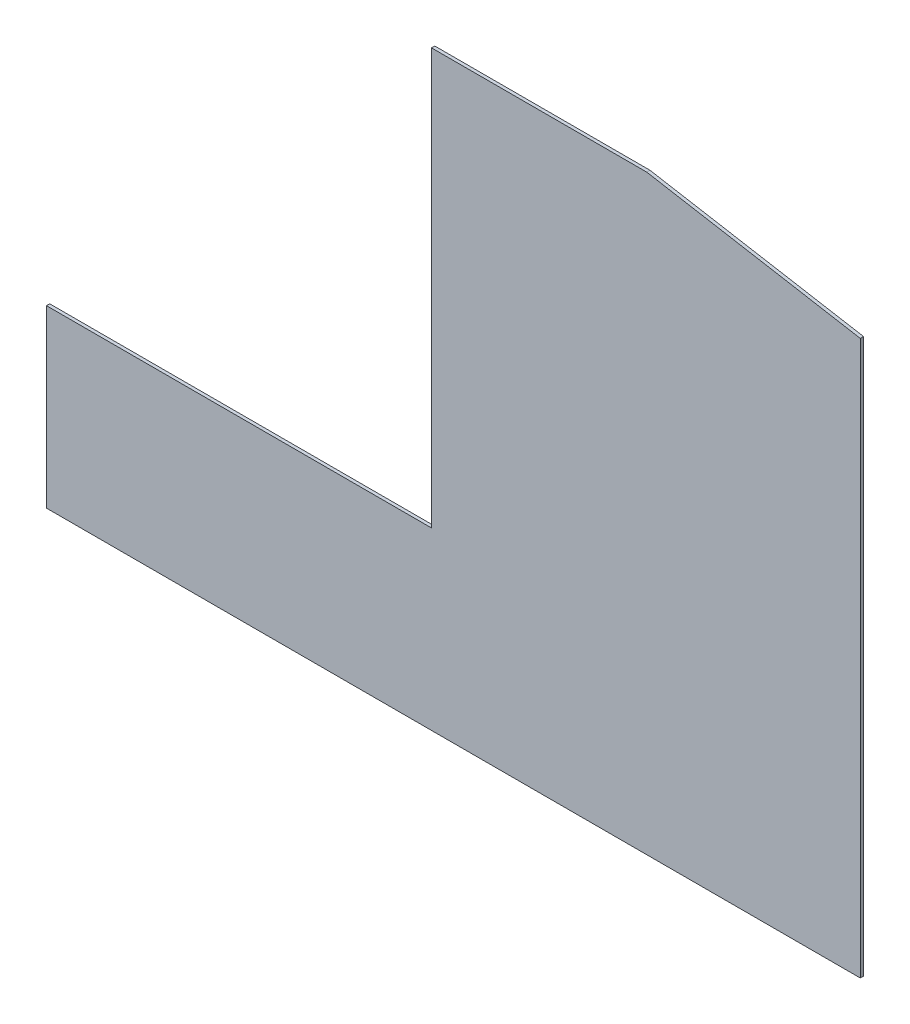
SolidWorks part; units mm, degrees
material "Hardox"
ref_plane "Ön Düzlem" through (0, 0, 0) normal (0, 0, 1) x (1, 0, 0)
ref_plane "Üst Düzlem" through (0, 0, 0) normal (0, 1, 0) x (1, 0, 0)
ref_plane "Sağ Düzlem" through (0, 0, 0) normal (1, 0, 0) x (0, 0, -1)
sketch "Çizim1" plane through (0, 0, 0) normal (0, 0, 1) x (1, 0, 0)
  line L0 (0, 0) -> (0, 1720)
  line L1 (0, 1720) -> (660, 1835)
  line L2 (660, 1835) -> (1855, 1835)
  line L3 (1855, 1835) -> (2515, 1720)
  line L4 (2515, 1720) -> (2515, 0)
  line L5 (2515, 0) -> (0, 0)
  dimension "D1" = 660
  dimension "D2" = 2515
  dimension "D3" = 660
  dimension "D4" = 1720
  dimension "D5" = 115
base flange "Taban-Flanş1" sketch "Çizim1" thickness 10 reverse thickness direction no parameters "D1"=6
sketch "Çizim6" plane through (0, 0, 0) normal (0, 0, 1) x (1, 0, 0)
  line L0 (1855, 1835) -> (660, 1835) construction
  line L1 (1190, 1835) -> (0, 1835)
  line L2 (1190, 1835) -> (1190, 550)
  line L3 (1190, 550) -> (0, 550)
  line L4 (0, 1835) -> (0, 550)
  line L5 (0, 1720) -> (0, 0) construction
  line L6 (0, 0) -> (2515, 0) construction
  line L7 (2515, 0) -> (2515, 1720) construction
  line L8 (0, 0) -> (2515, 0)
  line L9 (0, 0) -> (0, 8)
  line L10 (0, 8) -> (2515, 8)
  line L11 (2515, 0) -> (2515, 8)
  point P10 (0, 1720)
  point P11 (660, 1835)
  dimension "D1" = 550
  dimension "D2" = 1190
  dimension "D3" = 1285
  dimension "D4" = 115
  dimension "D5" = 660
  dimension "D6" = 542
  dimension "D7" = 1325
extrude "Kes-Ekstrüzyon1" cut sketch "Çizim6" against normal through all both and the other way through all
sketch "Çizim7" plane through (0, 0, 0) normal (0, 0, 1) x (1, 0, 0)
  line L0 (0, 8) -> (2515, 8) construction
  line L1 (0, 550) -> (1460, 550)
  line L2 (0, 550) -> (0, 8)
  line L3 (0, 8) -> (1460, 8)
  line L4 (1460, 550) -> (1460, 8)
  dimension "D1" = 1460
  dimension "D2" = 542
sketch "Büküm-Çizgileri1" [suppressed] plane through (0, 0, 0) normal (0, 1, 0) x (1, 0, 0)
sketch "Sınırlandırma-Kutusu1" [suppressed] plane through (0, 0, 0) normal (0, 1, 0) x (1, 0, 0)
sheet metal parameters "Sac-Levha1" thickness 10 parameters "D1"=6
flat pattern "Düz-Çoğaltma1" [suppressed]
sketch "Büküm-Çizgileri2" plane through (0, 0, 0) normal (0, 1, 0) x (1, 0, 0)
sketch3d "Sınırlandırma-Kutusu2" [suppressed]
  line L0 (0, 0, 0) -> (2515, 0, 0) construction
  line L1 (0, 1835, 0) -> (2515, 1835, 0) construction
  line L2 (0, 0, 0) -> (0, 1835, 0) construction
  line L3 (2515, 0, 0) -> (2515, 1835, 0) construction
sheet metal parameters "Sac-Levha2" thickness 10 parameters "D1"=6
flat pattern "Düz-Çoğaltma1"
sketch "Büküm-Çizgileri2" plane through (0, 0, 0) normal (0, 1, 0) x (1, 0, 0)
sketch3d "Sınırlandırma-Kutusu2" [suppressed]
  line L0 (0, 8, 0) -> (2515, 8, 0) construction
  line L1 (0, 1835, 0) -> (2515, 1835, 0) construction
  line L2 (0, 8, 0) -> (0, 1835, 0) construction
  line L3 (2515, 8, 0) -> (2515, 1835, 0) construction
